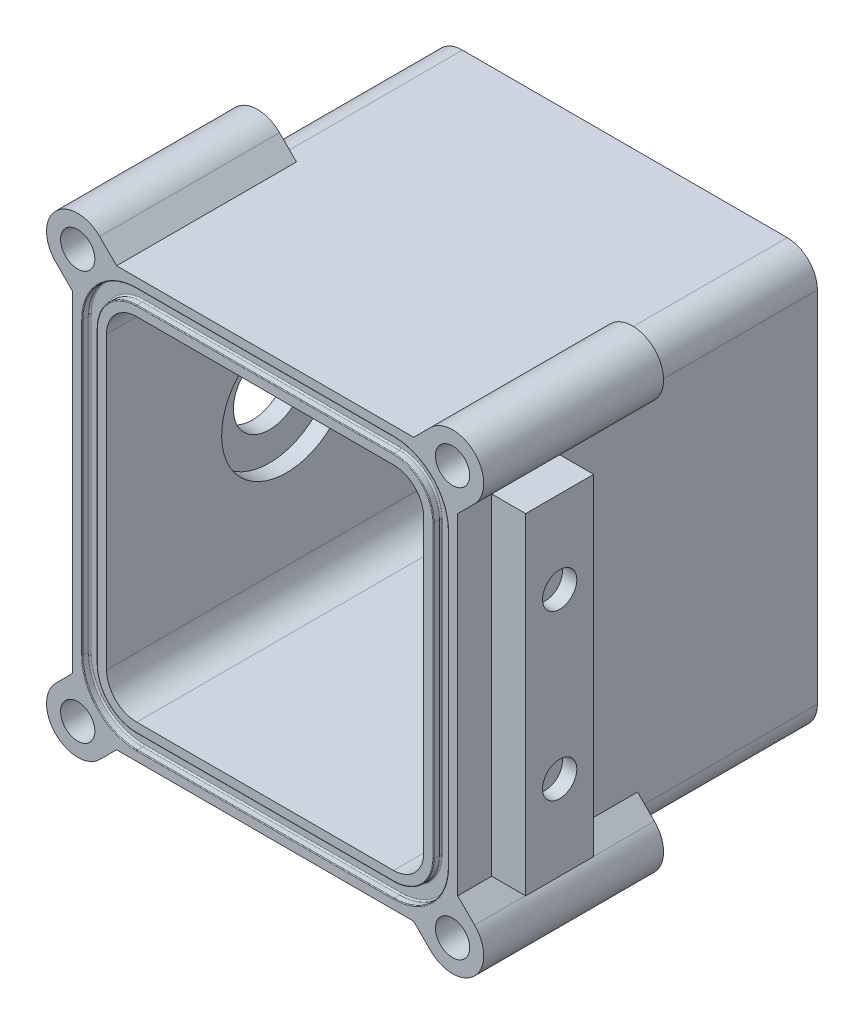
SolidWorks part; units mm, degrees
material "ABS"
ref_plane "X-Y Datum" through (0, 0, 0) normal (0, 0, 1) x (1, 0, 0)
ref_plane "X-Z Datum" through (0, 0, 0) normal (0, 1, 0) x (1, 0, 0)
ref_plane "Y-Z Datum" through (0, 0, 0) normal (1, 0, 0) x (0, 0, -1)
sketch "Sketch1" plane through (0, 0, 0) normal (0, 0, 1) x (1, 0, 0)
  line L0 (-34, -37) -> (-34, -16.68)
  line L1 (34, 37) -> (-34, 37)
  line L2 (34, 37) -> (34, -37)
  line L3 (34, -37) -> (-34, -37)
  line L5 (34, 37) -> (-34, -37) construction
  line L6 (34, -37) -> (-34, 37) construction
  line L7 (55.1739, 0) -> (-55.1739, 0) construction
  line L8 (-34, 37) -> (-34, 16.68)
  line L9 (-34, 16.68) -> (-34, -16.68)
  arc A0 (-34, -16.68) -> (-34, 16.68) centre (-14.8444, 0) cw construction
  point P0 (0, 0)
  dimension "D2" = 25.4
  dimension "D1" = 74
  dimension "D3" = 20.32
  dimension "D4" = 68
extrude "Boss-Extrude1" add sketch "Sketch1" along normal mid plane 63.5
shell "Shell1" thickness 6 removed face at (0, 0, 31.75)
fillet "Fillet1" radius 5.334 8 edges at (34, 37, 0) (34, -37, 0) (-34, -37, 0) (-34, 37, 0) (28, 31, 3) (28, -31, 3) (-28, -31, 3) (-28, 31, 3)
sketch "Sketch2" plane through (0, 0, 31.75) normal (0, 0, 1) x (1, 0, 0)
  line L21 (32.2827, -25.666) -> (32.2827, 25.666)
  line L22 (22.666, 35.2827) -> (-22.666, 35.2827)
  line L23 (-32.2827, 25.666) -> (-32.2827, -25.666)
  line L24 (-22.666, -35.2827) -> (22.666, -35.2827)
  line L25 (31, -25.666) -> (31, 25.666)
  line L26 (-22.666, -34) -> (22.666, -34)
  line L27 (-31, 25.666) -> (-31, -25.666)
  line L28 (22.666, 34) -> (-22.666, 34)
  line L29 (31, -25.666) -> (31, 25.666) construction
  line L30 (-22.666, -34) -> (22.666, -34) construction
  line L31 (-31, 25.666) -> (-31, -25.666) construction
  line L32 (22.666, 34) -> (-22.666, 34) construction
  line L33 (-29.7173, 25.666) -> (-29.7173, -25.666)
  line L34 (-22.666, -32.7173) -> (22.666, -32.7173)
  line L35 (29.7173, -25.666) -> (29.7173, 25.666)
  line L36 (22.666, 32.7173) -> (-22.666, 32.7173)
  arc A15 (32.2827, 25.666) -> (22.666, 35.2827) centre (22.666, 25.666) ccw
  arc A16 (-22.666, 35.2827) -> (-32.2827, 25.666) centre (-22.666, 25.666) ccw
  arc A17 (-32.2827, -25.666) -> (-22.666, -35.2827) centre (-22.666, -25.666) ccw
  arc A18 (22.666, -35.2827) -> (32.2827, -25.666) centre (22.666, -25.666) ccw
  arc A19 (31, 25.666) -> (22.666, 34) centre (22.666, 25.666) ccw
  arc A20 (22.666, -34) -> (31, -25.666) centre (22.666, -25.666) ccw
  arc A21 (-31, -25.666) -> (-22.666, -34) centre (-22.666, -25.666) ccw
  arc A22 (-22.666, 34) -> (-31, 25.666) centre (-22.666, 25.666) ccw
  arc A23 (31, 25.666) -> (22.666, 34) centre (22.666, 25.666) ccw construction
  arc A24 (22.666, -34) -> (31, -25.666) centre (22.666, -25.666) ccw construction
  arc A25 (-31, -25.666) -> (-22.666, -34) centre (-22.666, -25.666) ccw construction
  arc A26 (-22.666, 34) -> (-31, 25.666) centre (-22.666, 25.666) ccw construction
  arc A27 (-22.666, 32.7173) -> (-29.7173, 25.666) centre (-22.666, 25.666) ccw
  arc A28 (-29.7173, -25.666) -> (-22.666, -32.7173) centre (-22.666, -25.666) ccw
  arc A29 (22.666, -32.7173) -> (29.7173, -25.666) centre (22.666, -25.666) ccw
  arc A30 (29.7173, 25.666) -> (22.666, 32.7173) centre (22.666, 25.666) ccw
  dimension "D4" = 7.0513
  dimension "D5" = 2.5654
  dimension "D1" = 3
  dimension "D2" = 1.2827
  dimension "D3" = 1.2827
extrude "Cut-Extrude1" cut sketch "Sketch2" against normal blind 1.2954
fillet "Fillet2" radius 0.254 16 edges at (27.652, -30.652, 30.4546) (0, -32.7173, 30.4546) (-27.652, -30.652, 30.4546) (-29.7173, 0, 30.4546) (-27.652, 30.652, 30.4546) (0, 32.7173, 30.4546) (27.652, 30.652, 30.4546) (-29.466, 32.466, 30.4546) (0, 35.2827, 30.4546) (29.466, 32.466, 30.4546) (32.2827, 0, 30.4546) (29.466, -32.466, 30.4546) (0, -35.2827, 30.4546) (-29.466, -32.466, 30.4546) (29.7173, 0, 30.4546) (-32.2827, 0, 30.4546)
fillet "Fillet3" radius 0.127 16 edges at (-29.466, -32.466, 31.75) (-32.2827, 0, 31.75) (-29.466, 32.466, 31.75) (0, 35.2827, 31.75) (29.466, 32.466, 31.75) (32.2827, 0, 31.75) (29.466, -32.466, 31.75) (-27.652, -30.652, 31.75) (-29.7173, 0, 31.75) (-27.652, 30.652, 31.75) (0, 32.7173, 31.75) (27.652, 30.652, 31.75) (29.7173, 0, 31.75) (27.652, -30.652, 31.75) (0, -35.2827, 31.75) (0, -32.7173, 31.75)
sketch "Sketch3" plane through (0, 0, 31.75) normal (0, 0, 1) x (1, 0, 0)
  line L0 (22.666, -25.666) -> (37.7124, -40.7124) construction
  line L1 (29.2023, -39.9805) -> (26.2218, -37)
  line L2 (-28.666, -37) -> (28.666, -37) construction
  line L3 (22.666, -25.666) -> (0, 0)
  line L5 (34, -29.2218) -> (36.9805, -32.2023)
  line L6 (34, -31.666) -> (34, 31.666) construction
  arc A0 (22.666, -35.4097) -> (32.4097, -25.666) centre (22.666, -25.666) ccw construction
  arc A1 (22.666, -35.4097) -> (32.4097, -25.666) centre (22.666, -25.666) ccw
  circle A2 centre (33.0914, -36.0914) radius 3.025
  circle A3 centre (33.0914, -36.0914) radius 5.5
  point P7 (29.5558, -32.5558)
  arc M9 (32.4097, -25.666) -> (22.666, -35.4097) centre (22.666, -25.666) cw
  line M14 (-28.666, -37) -> (28.666, -37)
  arc M15 (28.666, -37) -> (34, -31.666) centre (28.666, -31.666) ccw
  line M16 (34, -31.666) -> (34, 31.666)
  dimension "D1" = 6.05
  dimension "D3" = 11
  dimension "D2" = 5
extrude "Boss-Extrude2" add sketch "Sketch3" against normal blind 31.75 contours L0 A2 A3 M15 M14 | A2 L0 A3 M16 M15 | L0 A2 M15 | L0 A2 M15 | A2 L0 M15 | A3 M14 | A3 M16 | A1 L0 A2 A3 M15 M16 | L0 A2 M15 | L0 A3 A2 M9 M14 M15 region at (32.0118, -32.0896, 31.75) region at (29.0896, -35.0118, 31.75) region at (32.4421, -34.0333, 31.75) region at (31.0333, -35.4421, 31.75) region at (34.789, -30.4552, 31.75) region at (36.5269, -35.0577, 31.75) region at (32.0577, -39.5269, 31.75) region at (27.4552, -37.789, 31.75) region at (34.5525, -35.5923, 31.75) region at (32.5923, -37.5525, 31.75)
sketch "Sketch4" plane through (0, 0, 31.75) normal (0, 0, 1) x (1, 0, 0)
  circle A0 centre (33.0914, -36.0914) radius 3.025 construction
  circle A1 centre (33.0914, -36.0914) radius 3.025
  dimension "D1" = 6.05
extrude "Cut-Extrude2" cut sketch "Sketch4" against normal blind 9
mirror "Mirror1" about plane through (0, 0, 0) normal (0, 1, 0) of "Cut-Extrude2", "Boss-Extrude2"
mirror "Mirror2" about plane through (0, 0, 0) normal (1, 0, 0) of "Mirror1", "Cut-Extrude2", "Boss-Extrude2"
sketch "Sketch8" plane through (-34, 0, 0) normal (-1, 0, 0) x (0, 0, 1)
  line L0 (19.75, 29.2218) -> (19.75, -29.2218) construction
  line L11 (25.75, 29.2218) -> (25.75, -29.2218)
  line L12 (0, 29.2218) -> (31.75, 29.2218) construction
  line L13 (0, -29.2218) -> (31.75, -29.2218) construction
  line L14 (25.75, 29.2218) -> (13.75, 29.2218)
  line L15 (13.75, 29.2218) -> (13.75, -29.2218)
  line L16 (13.75, -29.2218) -> (25.75, -29.2218)
  line L17 (13.75, 0) -> (25.75, 0) construction
  line L18 (25.75, 29.2218) -> (13.75, 29.2218)
  line L19 (25.75, -29.2218) -> (13.75, -29.2218)
  point P0 (0, 0)
  line M1 (31.75, 29.2218) -> (0, 29.2218)
  line M7 (0, -29.2218) -> (31.75, -29.2218)
extrude "Boss-Extrude3" add sketch "Sketch8" along normal blind 6 contours L15 L11 M1 M7 region at (-34, 0, 19.75)
sketch "Sketch12" plane through (-40, 0, 0) normal (-1, 0, 0) x (0, 0, 1)
  line L0 (19.75, 29.2218) -> (19.75, -29.2218) construction
  line L1 (25.75, 29.2218) -> (13.75, 29.2218) construction
  line L2 (13.75, -29.2218) -> (25.75, -29.2218) construction
  line L3 (13.75, 0) -> (25.75, 0) construction
  line L4 (13.75, 29.2218) -> (13.75, -29.2218) construction
  line L5 (25.75, 29.2218) -> (25.75, -29.2218) construction
  circle A0 centre (19.75, 14.6168) radius 3.025
  circle A1 centre (19.75, -14.3392) radius 3.025
  dimension "D1" = 14.605
  dimension "D3" = 6.05
  dimension "D2" = 6.05
extrude "Cut-Extrude6" cut sketch "Sketch12" against normal blind 2.54
sketch "Sketch13" plane through (-34, 0, 0) normal (-1, 0, 0) x (0, 0, 1)
  line L0 (-31.75, 0) -> (31.75, 0) construction
  line L3 (-31.75, 31.666) -> (-31.75, -31.666) construction
  line L4 (31.75, 29.2218) -> (31.75, -29.2218) construction
  circle A0 centre (0, 0) radius 6.35
  dimension "D2" = 12.7
extrude "Cut-Extrude10" cut sketch "Sketch13" against normal blind 6 contours A0 | A0 region at (-34, 0, 0)
sketch "Sketch16" plane through (-28, 0, 0) normal (1, 0, 0) x (0, 0, -1)
  circle A0 centre (0, 0) radius 11.43
  dimension "D1" = 22.86
extrude "Cut-Extrude14" cut sketch "Sketch16" against normal blind 3
mirror "Mirror5" about plane through (0, 0, 0) normal (1, 0, 0) of "Boss-Extrude3"
mirror "Mirror6" about plane through (0, 0, 0) normal (1, 0, 0) of "Cut-Extrude6"
